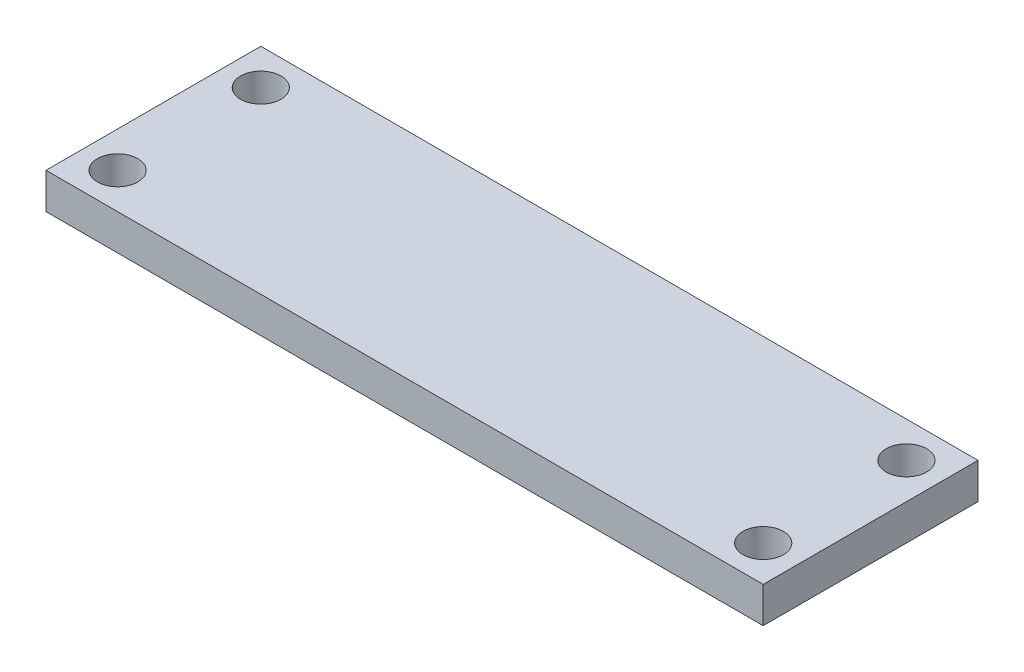
SolidWorks part; units mm, degrees
ref_plane "Front Plane" through (0, 0, 0) normal (0, 0, 1) x (1, 0, 0)
ref_plane "Top Plane" through (0, 0, 0) normal (0, 1, 0) x (1, 0, 0)
ref_plane "Right Plane" through (0, 0, 0) normal (1, 0, 0) x (0, 0, -1)
sketch "Sketch1" plane through (0, 0, 0) normal (0, 1, 0) x (1, 0, 0)
  line L0 (2, -2) -> (38.07, -2)
  line L1 (2, -2) -> (2, -10)
  line L2 (2, -10) -> (38.07, -10)
  line L3 (38.07, -2) -> (38.07, -10)
  line L4 (0, 0) -> (40.07, 0)
  line L5 (0, 0) -> (0, -12)
  line L6 (0, -12) -> (40.07, -12)
  line L7 (40.07, 0) -> (40.07, -12)
  circle A0 centre (2, -2) radius 1.1303
  circle A1 centre (38.07, -2) radius 1.1303
  circle A2 centre (38.07, -10) radius 1.1303
  circle A3 centre (2, -10) radius 1.1303
  circle A4 centre (2, -2) radius 1.7907 construction
  circle A5 centre (2, -10) radius 1.7907 construction
  circle A6 centre (38.07, -10) radius 1.7907 construction
  circle A7 centre (38.07, -2) radius 1.7907 construction
  dimension "D3" = 2.2606
  dimension "D1" = 3.5814
  dimension "D2" = 36.07
  dimension "D4" = 8
  dimension "D5" = 2
  dimension "D6" = 2
  dimension "D7" = 2
  dimension "D8" = 2
extrude "Boss-Extrude1" add sketch "Sketch1" along normal blind 2 contours L7 L4 L5 L6 A3 L1 A0 L0 A1 L3 A2 L2 | A3 L2 A2 L3 A1 L0 A0 L1 region at (20.035, 0, 6) region at (20.035, 0, 0.4183)
equation "\"D7@Sketch1\"=\"D5@Sketch1\""
equation "\"D8@Sketch1\"=\"D5@Sketch1\""
equation "\"D6@Sketch1\"=\"D5@Sketch1\""
